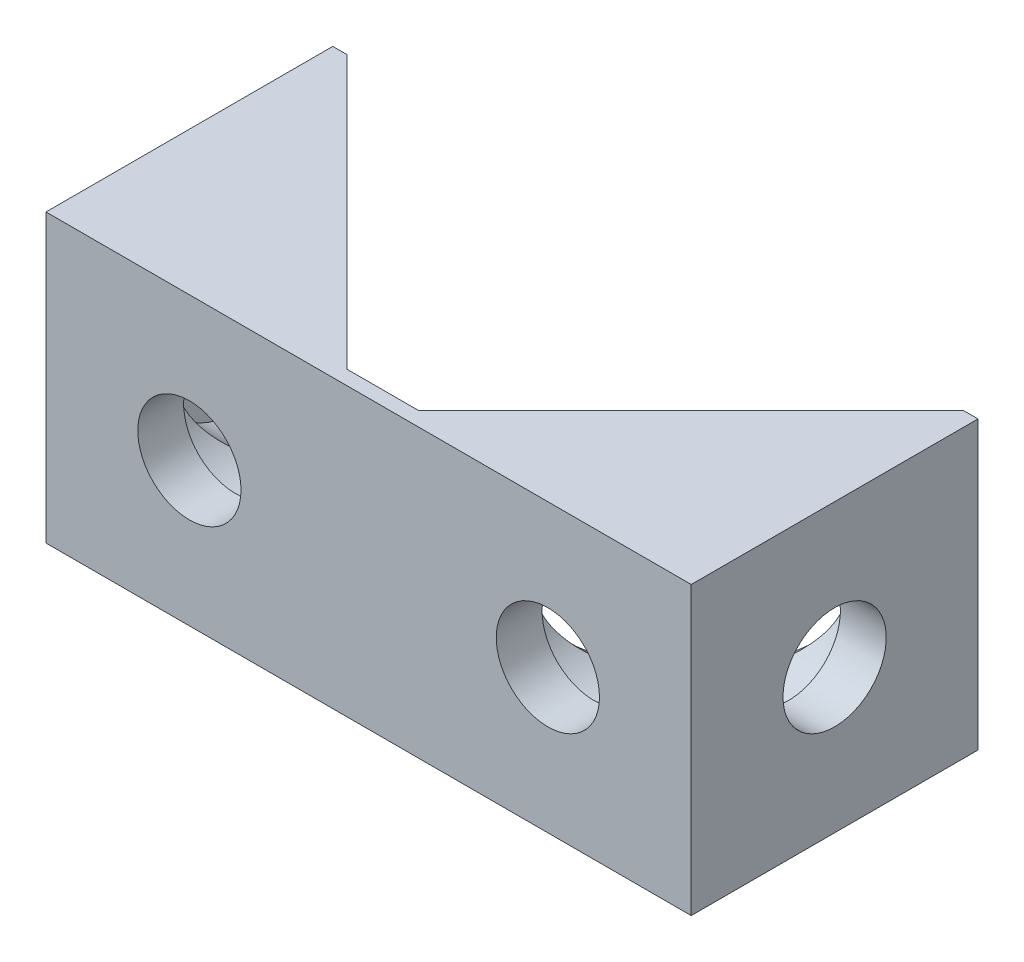
SolidWorks part; units mm, degrees
ref_plane "Front Plane" through (0, 0, 0) normal (0, 0, 1) x (1, 0, 0)
ref_plane "Top Plane" through (0, 0, 0) normal (0, 1, 0) x (1, 0, 0)
ref_plane "Right Plane" through (0, 0, 0) normal (1, 0, 0) x (0, 0, -1)
sketch "Sketch2" plane through (0, 0, 0) normal (0, 1, 0) x (1, 0, 0)
  line L0 (0, 0) -> (0, 20)
  line L2 (20, 0) -> (0, 0)
  line L3 (0, 20) -> (1, 20)
  line L5 (1, 20) -> (20, 1)
  line L6 (20, 0) -> (25, 0) construction
  line L7 (22.5, -22.7885) -> (22.5, 22.7885) construction
  line L8 (44, 20) -> (25, 1)
  line L10 (45, 20) -> (44, 20)
  line L11 (25, 0) -> (45, 0)
  line L12 (45, 0) -> (45, 20)
  line L13 (20, 1) -> (25, 1)
  line L14 (20, 0) -> (25, 0)
  point P9 (22.5, 0)
  point P10 (22.5, 0)
  dimension "D1" = 20
  dimension "D2" = 1
  dimension "D3" = 5
  dimension "D4" = 1
extrude "Boss-Extrude1" add sketch "Sketch2" along normal mid plane 20
sketch "Sketch3" plane through (0, 0, 0) normal (0, 0, 1) x (1, 0, 0)
  line L0 (0, 10) -> (20, -10) construction
  line L1 (20, 10) -> (0, 0) construction
  line L2 (0, 10) -> (45, 10) construction
  line L3 (0, -10) -> (45, -10) construction
  line L4 (22.5, 10) -> (22.5, -10) construction
  circle A0 centre (10, 0) radius 3.6
  circle A1 centre (10, 0) radius 5.5
  circle A2 centre (35, 0) radius 3.6
  circle A3 centre (35, 0) radius 5.5
  dimension "D1" = 7.2
  dimension "D2" = 11
extrude "Cut-Extrude1" cut sketch "Sketch3" against normal up to surface (20 mm away) contours A0 | A2 region at (10, 0, 0) up to face at (0.5, 0, -20)
extrude "Cut-Extrude3" cut sketch "Sketch3<4>" against normal up to surface (20 mm away) from offset 3.2 up to face at (0.5, 0, -20) offset against normal yes
sketch "Sketch3<4>" plane through (0, 0, 0) normal (0, 0, 1) x (1, 0, 0) same geometry as "Sketch3"
sketch "Sketch4" plane through (0, 0, 0) normal (-1, 0, 0) x (0, 0, 1)
  line L0 (-20, 10) -> (0, -10) construction
  line L1 (0, 10) -> (-20, -10) construction
  circle A0 centre (-10, 0) radius 3.6
  circle A1 centre (-10, 0) radius 5.5
  point P11 (-10, 0)
  dimension "D1" = 7.2
  dimension "D2" = 11
extrude "Cut-Extrude2" cut sketch "Sketch4" against normal up to surface (45 mm away) contours A0 region at (0, 0, -10) up to face at (45, 0, -10)
extrude "Cut-Extrude4" cut sketch "Sketch4<3>" against normal offset from surface (38.6 mm away) 3.2 from offset 3.2 up to face at (45, 0, -6.4) offset against normal yes
sketch "Sketch4<3>" plane through (0, 0, 0) normal (-1, 0, 0) x (0, 0, 1) same geometry as "Sketch4"
